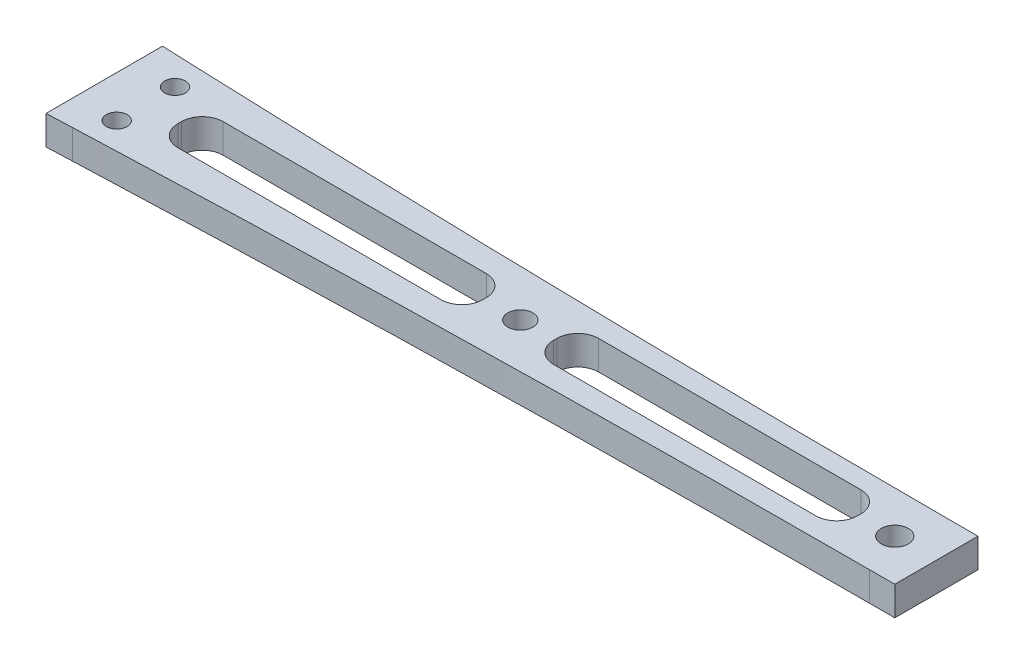
SolidWorks part; units mm, degrees
ref_plane "Płaszczyzna przednia" through (0, 0, 0) normal (0, 0, 1) x (1, 0, 0)
ref_plane "Płaszczyzna górna" through (0, 0, 0) normal (0, 1, 0) x (1, 0, 0)
ref_plane "Płaszczyzna prawa" through (0, 0, 0) normal (1, 0, 0) x (0, 0, -1)
sketch "Szkic1" plane through (0, 0, 0) normal (0, 1, 0) x (1, 0, 0)
  line L0 (100, 0) -> (100, 10)
  line L4 (200, 0) -> (200, 20)
  line L5 (0, 10) -> (10, 10)
  line L6 (200, 10) -> (190, 10)
  line L8 (22.9848, 15.5746) -> (86.2594, 15.5746)
  line L9 (17.9848, 10.5746) -> (17.9848, 9.6967)
  line L10 (22.9848, 4.6967) -> (86.2594, 4.6967)
  line L11 (91.2594, 10.5746) -> (91.2594, 9.6967)
  line L12 (113.2251, 15.5746) -> (176.2862, 15.5746)
  line L13 (108.2251, 10.5746) -> (108.2251, 9.7528)
  line L14 (113.2251, 4.7528) -> (176.2862, 4.7528)
  line L15 (181.2862, 10.5746) -> (181.2862, 9.7528)
  line L16 (10, 3) -> (10, 17)
  line L17 (0, -4) -> (100, 0)
  line L18 (200, 0) -> (100, 0)
  line L19 (200, 20) -> (100, 20)
  line L20 (100, 20) -> (0, 24)
  line L21 (0, 24) -> (0, -4)
  circle A0 centre (100, 10) radius 3
  circle A2 centre (190, 10) radius 3.25
  arc A3 (176.2862, 4.7528) -> (181.2862, 9.7528) centre (176.2862, 9.7528) ccw
  arc A4 (181.2862, 10.5746) -> (176.2862, 15.5746) centre (176.2862, 10.5746) ccw
  arc A5 (113.2251, 4.7528) -> (108.2251, 9.7528) centre (113.2251, 9.7528) cw
  arc A6 (113.2251, 15.5746) -> (108.2251, 10.5746) centre (113.2251, 10.5746) ccw
  arc A7 (17.9848, 9.6967) -> (22.9848, 4.6967) centre (22.9848, 9.6967) ccw
  arc A8 (86.2594, 4.6967) -> (91.2594, 9.6967) centre (86.2594, 9.6967) ccw
  arc A9 (91.2594, 10.5746) -> (86.2594, 15.5746) centre (86.2594, 10.5746) ccw
  arc A10 (22.9848, 15.5746) -> (17.9848, 10.5746) centre (22.9848, 10.5746) ccw
  circle A11 centre (10, 17) radius 2.5
  circle A12 centre (10, 3) radius 2.5
  point P39 (0, 10)
  point P42 (10, 10)
  dimension "D1" = 5
extrude "Dodanie-wyciągnięcie1" add sketch "Szkic1" along normal blind 7 contours A0 L4 region at (49.9193, 0, -0.0179)
fillet "Zaokrąglenie1" radius 4700 2 edges at (100, 3.5, -20) (100, 3.5, 0)
